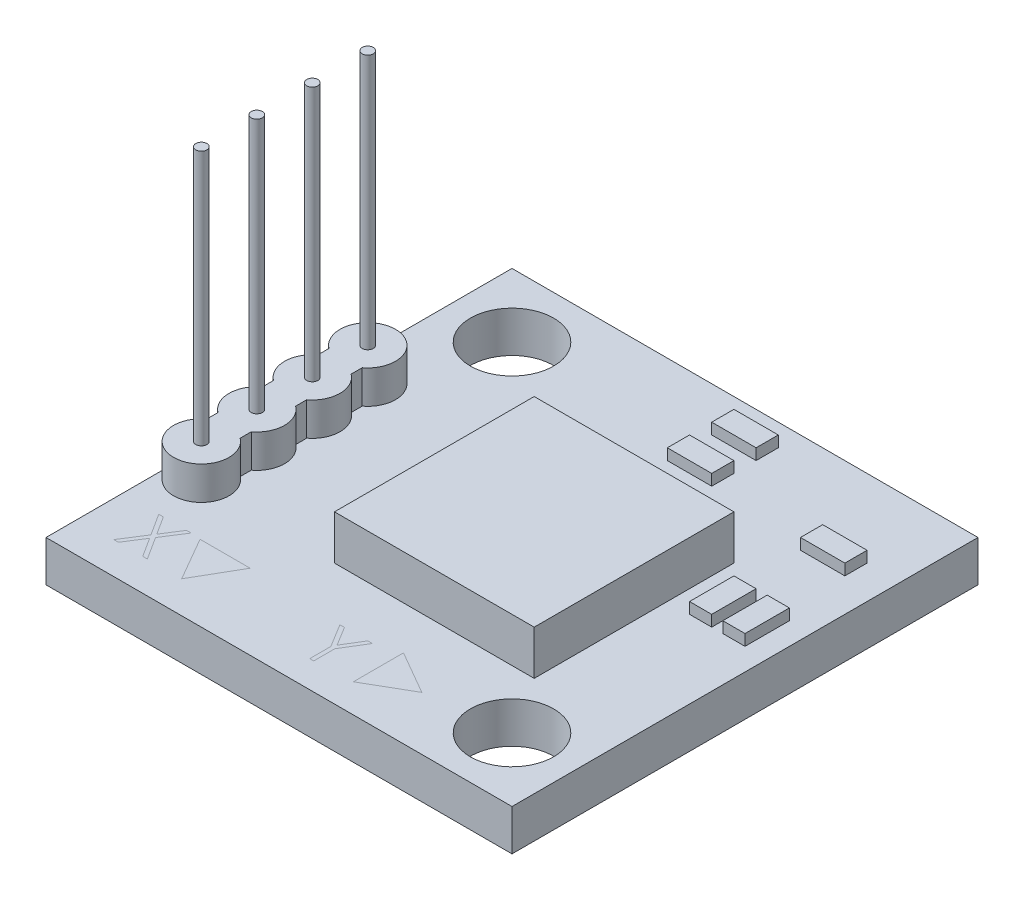
SolidWorks part; units mm, degrees
ref_plane "Plano frontal" through (0, 0, 0) normal (0, 0, 1) x (1, 0, 0)
ref_plane "Plano superior" through (0, 0, 0) normal (0, 1, 0) x (1, 0, 0)
ref_plane "Plano direito" through (0, 0, 0) normal (1, 0, 0) x (0, 0, -1)
sketch "Sketch1" plane through (0, 0, 0) normal (0, 1, 0) x (1, 0, 0)
  line L1 (-10.5, -10.5) -> (10.5, -10.5)
  line L2 (-10.5, -10.5) -> (-10.5, 10.5)
  line L3 (-10.5, 10.5) -> (10.5, 10.5)
  line L4 (10.5, -10.5) -> (10.5, 10.5)
  line L5 (-10.5, -10.5) -> (10.5, 10.5) construction
  line L6 (-10.5, 10.5) -> (10.5, -10.5) construction
  point P0 (0, 0)
  dimension "D1" = 21
extrude "Boss-Extrude1" add sketch "Sketch1" along normal blind 1.85
sketch "Sketch2" plane through (0, 1.85, 0) normal (0, 1, 0) x (1, 0, 0)
  line L0 (-10.5, -10.5) -> (10.5, -10.5) construction
  line L1 (-3, 4) -> (6, 4)
  line L2 (-3, 4) -> (-3, -5)
  line L3 (-3, -5) -> (6, -5)
  line L4 (6, 4) -> (6, -5)
  line L5 (-3, 4) -> (6, -5) construction
  line L6 (-3, -5) -> (6, 4) construction
  line L7 (10.5, -10.5) -> (10.5, 10.5) construction
  point P0 (1.5, -0.5)
  dimension "D1" = 9
  dimension "D2" = 5.5
  dimension "D3" = 4.5
extrude "Boss-Extrude2" add sketch "Sketch2" along normal blind 2
sketch "Sketch3" plane through (0, 1.85, 0) normal (0, 1, 0) x (1, 0, 0)
  line L0 (10.5, -10.5) -> (10.5, 10.5) construction
  line L1 (-10.5, -10.5) -> (10.5, -10.5) construction
  line L2 (10.5, 10.5) -> (-10.5, 10.5) construction
  line L3 (-10.5, 10.5) -> (-10.5, -10.5) construction
  circle A0 centre (7.625, -7.625) radius 1.875
  circle A1 centre (-7.625, 7.625) radius 1.875
  dimension "D1" = 3.75
  dimension "D3" = 2.875
  dimension "D2" = 2.875
  dimension "D4" = 2.875
  dimension "D5" = 2.875
extrude "Cut-Extrude1" cut sketch "Sketch3" against normal up to surface (1.85 mm away) up to face at (0, 0, 0)
sketch "Sketch4" plane through (0, 1.85, 0) normal (0, 1, 0) x (1, 0, 0)
  line L1 (0.5, 9.5) -> (2.5, 9.5)
  line L2 (0.5, 9.5) -> (0.5, 8.5)
  line L3 (0.5, 8.5) -> (2.5, 8.5)
  line L4 (2.5, 9.5) -> (2.5, 8.5)
  line L5 (0.5, 9.5) -> (2.5, 8.5) construction
  line L6 (0.5, 8.5) -> (2.5, 9.5) construction
  line L7 (0.5, 7.5) -> (2.5, 7.5)
  line L8 (0.5, 7.5) -> (0.5, 6.5)
  line L9 (0.5, 6.5) -> (2.5, 6.5)
  line L10 (2.5, 7.5) -> (2.5, 6.5)
  line L11 (7, 7) -> (9, 7)
  line L12 (7, 7) -> (7, 6)
  line L13 (7, 6) -> (9, 6)
  line L14 (9, 7) -> (9, 6)
  line L15 (7, 3) -> (8, 3)
  line L16 (7, 3) -> (7, 1)
  line L17 (7, 1) -> (8, 1)
  line L18 (8, 3) -> (8, 1)
  line L19 (8.5, 3) -> (9.5, 3)
  line L20 (8.5, 3) -> (8.5, 1)
  line L21 (8.5, 1) -> (9.5, 1)
  line L22 (9.5, 3) -> (9.5, 1)
  line L23 (10.5, 10.5) -> (-10.5, 10.5) construction
  line L24 (10.5, -10.5) -> (10.5, 10.5) construction
  line L25 (6, 4) -> (-3, 4) construction
  point P0 (1.5, 9)
  point P25 (7, 6.5)
  point P28 (9, 3)
  dimension "D1" = 2
  dimension "D2" = 1
  dimension "D3" = 1
  dimension "D4" = 1
  dimension "D5" = 10
  dimension "D6" = 1.5
  dimension "D7" = 1
  dimension "D8" = 0.5
extrude "Boss-Extrude3" add sketch "Sketch4" along normal blind 0.5
sketch "Sketch5" plane through (0, 0, 0) normal (0, 1, 0) x (1, 0, 0)
  line L0 (-10.5, 10.5) -> (-10.5, -10.5) construction
  line L1 (-10.5, -10.5) -> (10.5, -10.5) construction
  circle A0 centre (-9.25, 2.75) radius 0.75
  circle A1 centre (-9.25, 0.25) radius 0.75
  circle A2 centre (-9.25, -2.25) radius 0.75
  circle A3 centre (-9.25, -4.75) radius 0.75
  dimension "D1" = 1.5
  dimension "D2" = 4
  dimension "D3" = 1.25
  dimension "D4" = 13.25
extrude "Boss-Extrude4" add sketch "Sketch5" against normal blind 2 draft 10
sketch "Sketch6" plane through (0, 1.85, 0) normal (0, -1, 0) x (1, 0, 0)
  line L0 (-10, -1.25) -> (-10, -1.75)
  line L2 (-8.5, 3.75) -> (-8.5, 3.25)
  line L3 (-8.5, -1.25) -> (-8.5, -1.75)
  line L4 (-10, 3.75) -> (-10, 3.25)
  line L5 (-8.5, 1.25) -> (-8.5, 0.75)
  line L6 (-10, 1.25) -> (-10, 0.75)
  arc A0 (-10, -1.75) -> (-8.5, -1.75) centre (-9.25, -2.75) ccw
  arc A1 (-8.5, -1.25) -> (-8.5, 0.75) centre (-9.25, -0.25) ccw
  arc A2 (-8.5, 1.25) -> (-8.5, 3.25) centre (-9.25, 2.25) ccw
  arc A3 (-8.5, 3.75) -> (-10, 3.75) centre (-9.25, 4.75) ccw
  circle A4 centre (-9.25, 4.75) radius 1.0762 construction
  circle A5 centre (-9.25, 2.25) radius 1.0762 construction
  circle A6 centre (-9.25, -0.25) radius 1.0762 construction
  circle A7 centre (-9.25, -2.75) radius 1.0762 construction
  arc A8 (-10, 0.75) -> (-10, -1.25) centre (-9.25, -0.25) ccw
  arc A9 (-10, 3.25) -> (-10, 1.25) centre (-9.25, 2.25) ccw
  dimension "D1" = 2.5
  dimension "D2" = 1.5
extrude "Boss-Extrude5" add sketch "Sketch6" against normal blind 1.5
sketch "Sketch7" plane through (0, 3.35, 0) normal (0, 1, 0) x (-1, 0, 0)
  circle A0 centre (9.25, -2.75) radius 0.25
  circle A1 centre (9.25, -0.25) radius 0.25
  circle A2 centre (9.25, 2.25) radius 0.25
  circle A3 centre (9.25, 4.75) radius 0.25
  dimension "D1" = 0.5
extrude "Boss-Extrude6" add sketch "Sketch7" along normal blind 11.5
sketch "Sketch8" plane through (0, 1.85, 0) normal (0, 1, 0) x (1, 0, 0)
  line L1 (-5.8296, -9.0557) -> (-4.7008, -7.1005)
  line L2 (-4.7008, -7.1005) -> (-6.9584, -7.1005)
  line L3 (-6.9584, -7.1005) -> (-5.8296, -9.0557)
  line L4 (4.0154, -8.0781) -> (2.0583, -6.9481)
  line L5 (2.0583, -6.9481) -> (2.0583, -9.2081)
  line L6 (2.0583, -9.2081) -> (4.0154, -8.0781)
  circle A0 centre (-5.8296, -7.7523) radius 0.6517 construction
  circle A1 centre (2.7107, -8.0781) radius 0.6524 construction
  text T0 "Y" font "Century Gothic" height 2
  text T1 "X" font "Century Gothic" height 2
split line "Split Line2"
equation "\"D2@Sketch3\"=\"D1@Sketch3\"/2+1"
equation "\"D3@Sketch3\"=\"D2@Sketch3\""
equation "\"D4@Sketch3\"=\"D3@Sketch3\""
equation "\"D5@Sketch3\"=\"D4@Sketch3\""
equation "\"D3@Sketch4\"=\"D2@Sketch4\""
equation "\"D4@Sketch4\"=\"D3@Sketch4\""
